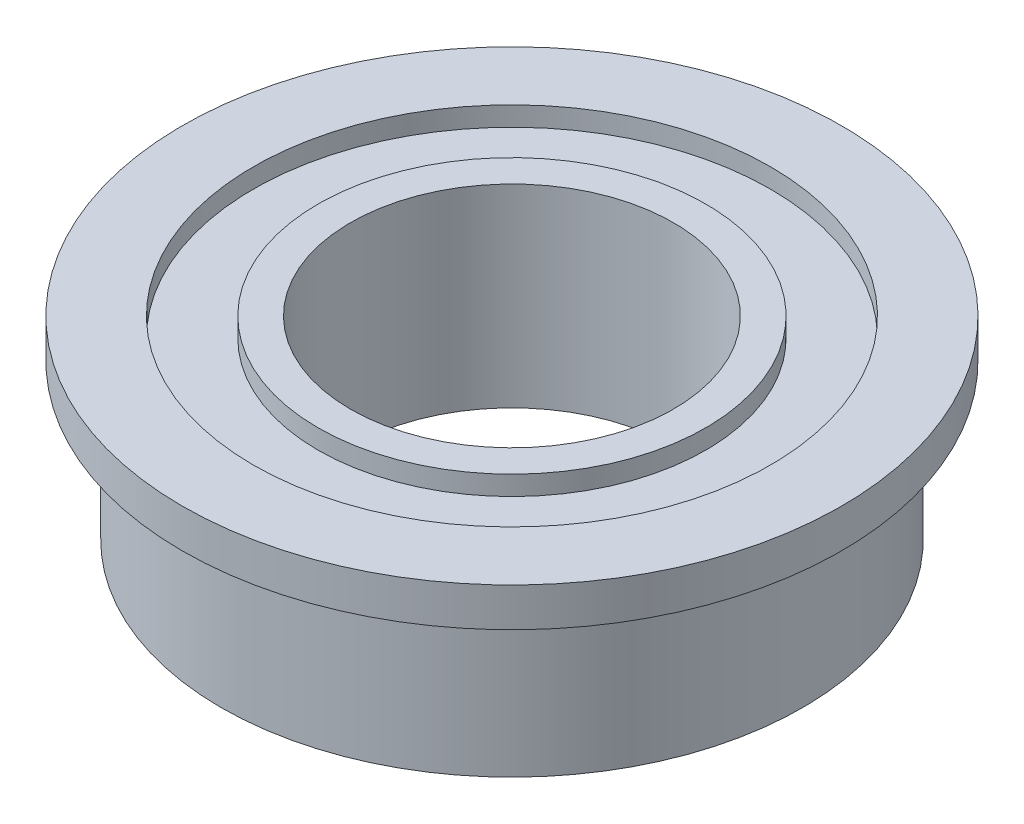
SolidWorks part; units mm, degrees
ref_plane "前视基准面" through (0, 0, 0) normal (0, 0, 1) x (1, 0, 0)
ref_plane "上视基准面" through (0, 0, 0) normal (0, 1, 0) x (1, 0, 0)
ref_plane "右视基准面" through (0, 0, 0) normal (1, 0, 0) x (0, 0, -1)
other "Configuration Table"
sketch "草图1" plane through (0, 0, 0) normal (0, 1, 0) x (1, 0, 0)
  circle A0 centre (0, 0) radius 2.5
  circle A1 centre (0, 0) radius 3
  circle A2 centre (0, 0) radius 4
  circle A3 centre (0, 0) radius 4.5
  dimension "D1" = 5
  dimension "D2" = 0.5
  dimension "D3" = 9
  dimension "D4" = 8
extrude "凸台-拉伸1" add sketch "草图1" along normal blind 1.5 and the other way blind 1.5 contours A3 A2 | A1 A0 region at (-2.9151, 0, 0) region at (-4.3727, 0, 0)
sketch "草图2" plane through (0, 0, 0) normal (0, 1, 0) x (1, 0, 0)
  circle A0 centre (0, 0) radius 3
  circle A1 centre (0, 0) radius 4
  circle A2 centre (0, 0) radius 3 construction
  circle A3 centre (0, 0) radius 4 construction
extrude "凸台-拉伸2" add sketch "草图2" along normal blind 1.2 and the other way blind 1.2
sketch "草图3" plane through (0, 1.5, 0) normal (0, 1, 0) x (1, 0, 0)
  circle A0 centre (0, 0) radius 5.1
  circle A1 centre (0, 0) radius 4.5
  circle A2 centre (0, 0) radius 4.5 construction
  dimension "D1" = 10.2
extrude "凸台-拉伸3" add sketch "草图3" against normal blind 0.6
